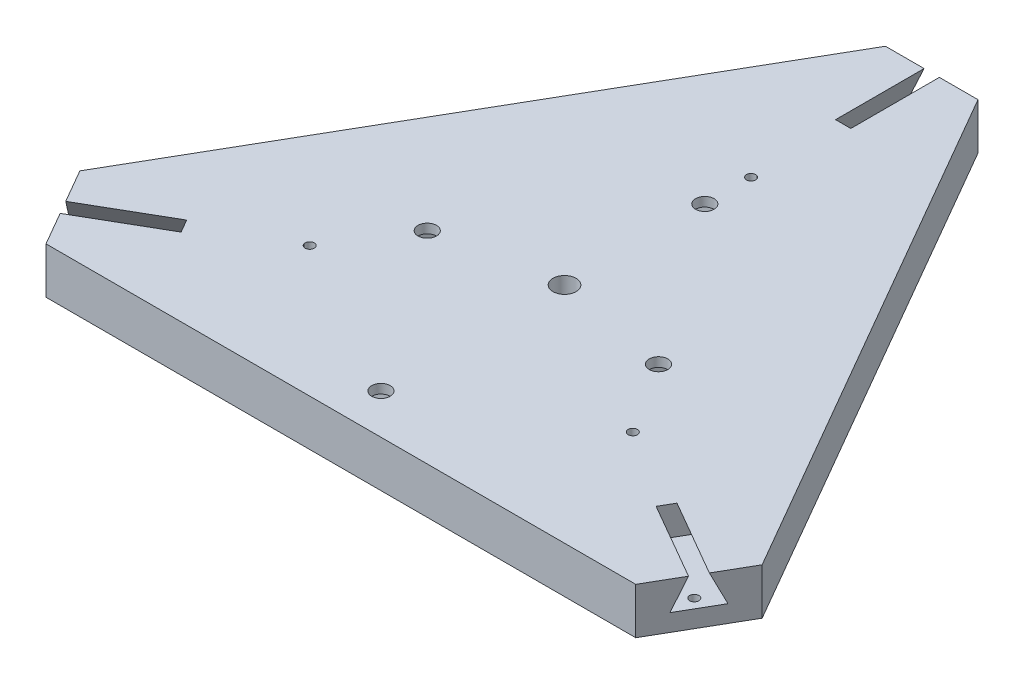
SolidWorks part; units mm, degrees
material "PLA"
ref_plane "Plan de face" through (0, 0, 0) normal (0, 0, 1) x (1, 0, 0)
ref_plane "Plan de dessus" through (0, 0, 0) normal (0, 1, 0) x (1, 0, 0)
ref_plane "Plan de droite" through (0, 0, 0) normal (1, 0, 0) x (0, 0, -1)
sketch "Esquisse1" plane through (0, 0, 0) normal (0, 1, 0) x (1, 0, 0)
  line L29 (-10, 79.3725) -> (10, 79.3725)
  line L30 (73.7386, -31.026) -> (63.7386, -48.3465)
  line L31 (-63.7386, -48.3465) -> (-73.7386, -31.026)
  line L32 (-10, 79.3725) -> (-73.7386, -31.026)
  line L33 (-63.7386, -48.3465) -> (63.7386, -48.3465)
  line L34 (73.7386, -31.026) -> (10, 79.3725)
  circle A7 centre (0, 0) radius 2.5
  circle A8 centre (0, 0) radius 79.3725 construction
  point P17 (0, 0)
  dimension "D1" = 20
  dimension "D4" = 20
  dimension "D5" = 80
  dimension "D6" = 80
  dimension "D3" = 80
  dimension "D9" = 5
  dimension "D12" = 79.3725
  dimension "D2" = 20
  dimension "D7" = 60
  dimension "D8" = 60
  dimension "D10" = 80
  dimension "D11" = 80
extrude "Boss.-Extru.1" add sketch "Esquisse1" along normal mid plane 10
sketch "Esquisse2" plane through (0, 5, 0) normal (0, 1, 0) x (1, 0, 0)
  line L0 (-68.7386, -39.6863) -> (0, 0) construction
  line L1 (-73.7386, -31.026) -> (-63.7386, -48.3465) construction
  circle A0 centre (-66.3571, -38.3113) radius 1
  circle A1 centre (-34.9203, -20.1613) radius 1
  dimension "D1" = 2
  dimension "D4" = 2
  dimension "D2" = 2.75
  dimension "D3" = 39.05
extrude "Enlèv. mat.-Extru.1" cut sketch "Esquisse2" against normal through all
pattern_circular "Répétition circulaire1" count 3 over 360 about axis through (0, 5, 0) along (0, -1, 0) of "Enlèv. mat.-Extru.1" reverse direction yes
sketch "Esquisse3" plane through (68.7386, 0, 39.6863) normal (0.866, 0, 0.5) x (0.5, 0, -0.866)
  line L0 (1.65, 5) -> (4.59, -1.29)
  line L1 (-10, 5) -> (10, 5) construction
  line L3 (-4.59, -1.29) -> (-1.65, 5)
  line L4 (-1.65, 5) -> (1.65, 5)
  line L7 (-4.59, -1.29) -> (4.59, -1.29)
  line L8 (-10, -5) -> (10, -5) construction
  point P6 (0, 5)
  point P11 (0, 0)
  dimension "D1" = 3.3
  dimension "D2" = 6.29
  dimension "D3" = 9.18
extrude "Enlèv. mat.-Extru.2" cut sketch "Esquisse3" against normal blind 19.14
pattern_circular "Répétition circulaire2" count 3 over 360 about axis through (0, 5, 0) along (0, -1, 0) of "Enlèv. mat.-Extru.2"
sketch "Esquisse4" plane through (0, -5, 0) normal (0, -1, 0) x (1, 0, 0)
  line L0 (0, 0) -> (25, 0) construction
  line L1 (25, 0) -> (25, 4.68) construction
  line L2 (0, 0) -> (-25, 0) construction
  line L3 (-25, 0) -> (-25, 4.68) construction
  circle A3 centre (0, -30.3225) radius 2
  circle A4 centre (0, -40.3225) radius 1 construction
  circle A7 centre (0, 39.68) radius 2
  circle A8 centre (25, 4.68) radius 2
  circle A9 centre (-25, 4.68) radius 2
  point P7 (0, 0)
  point P15 (0, 0)
  dimension "D3" = 25
  dimension "D4" = 4.68
  dimension "D7" = 4
  dimension "D8" = 39.68
  dimension "D1" = 10
  dimension "D2" = 4
  dimension "D5" = 25
  dimension "D9" = 4
  dimension "D10" = 4
  dimension "D6" = 4.68
extrude "Enlèv. mat.-Extru.3" cut sketch "Esquisse4" against normal through all
sketch "Esquisse5" plane through (0, -5, 0) normal (0, -1, 0) x (1, 0, 0)
  line L0 (-19.85, 34.53) -> (19.85, 34.53)
  line L1 (-19.85, 34.53) -> (-19.85, -25.1725)
  line L2 (-19.85, -25.1725) -> (19.85, -25.1725)
  line L3 (19.85, -25.1725) -> (19.85, 34.53)
  line L4 (-30.15, 44.83) -> (30.15, 44.83)
  line L5 (30.15, -35.4725) -> (30.15, 44.83)
  line L6 (-30.15, -35.4725) -> (30.15, -35.4725)
  line L7 (-30.15, 44.83) -> (-30.15, -35.4725)
  circle A0 centre (25, 4.68) radius 2 construction
  circle A1 centre (-25, 4.68) radius 2 construction
  circle A2 centre (0, 39.68) radius 2 construction
  circle A3 centre (0, -30.3225) radius 2 construction
  dimension "D1" = 5.15
  dimension "D2" = 5.15
  dimension "D3" = 5.15
  dimension "D4" = 5.15
  dimension "D5" = 10.3
extrude "Enlèv. mat.-Extru.4" cut sketch "Esquisse5" against normal blind 8
sketch "Esquisse6" plane through (0, -5, 0) normal (0, -1, 0) x (1, 0, 0)
  line L4 (19.85, 34.53) -> (-19.85, 34.53) construction
  circle A0 centre (0, 20.18) radius 3.325
  circle A1 centre (0, 20.18) radius 6.325
  dimension "D2" = 6.65
  dimension "D3" = 3
  dimension "D1" = 14.35
extrude "Boss.-Extru.2" add sketch "Esquisse6" along normal blind 10
